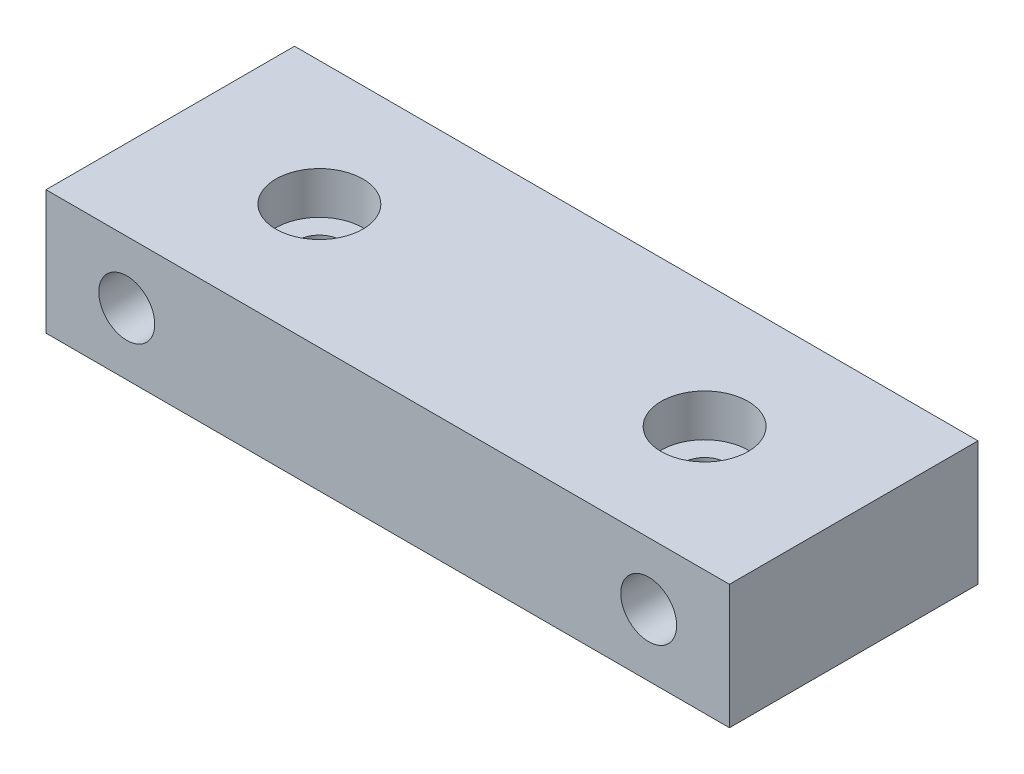
SolidWorks part; units mm, degrees
material "ABS"
ref_plane "Front Plane" through (0, 0, 0) normal (0, 0, 1) x (1, 0, 0)
ref_plane "Top Plane" through (0, 0, 0) normal (0, 1, 0) x (1, 0, 0)
ref_plane "Right Plane" through (0, 0, 0) normal (1, 0, 0) x (0, 0, -1)
sketch "Sketch1" plane through (0, 0, 0) normal (0, 1, 0) x (1, 0, 0)
  line L1 (-27.5, -10) -> (27.5, -10)
  line L2 (-27.5, -10) -> (-27.5, 10)
  line L3 (-27.5, 10) -> (27.5, 10)
  line L4 (27.5, -10) -> (27.5, 10)
  line L5 (-27.5, -10) -> (27.5, 10) construction
  line L6 (-27.5, 10) -> (27.5, -10) construction
  point P0 (0, 0)
  dimension "D1" = 55
  dimension "D2" = 20
extrude "Boss-Extrude1" add sketch "Sketch1" along normal blind 10
sketch "Sketch2" plane through (0, 0, 10) normal (0, 0, 1) x (1, 0, 0)
  line L0 (-27.5, 0) -> (27.5, 0) construction
  line L1 (-27.5, 10) -> (-27.5, 0) construction
  circle A0 centre (-21, 5) radius 2.25
  circle A1 centre (21, 5) radius 2.25
  dimension "D1" = 4.5
  dimension "D4" = 4.5
  dimension "D2" = 5
  dimension "D3" = 6.5
  dimension "D5" = 42
extrude "Cut-Extrude1" cut sketch "Sketch2" against normal through all
sketch "Sketch3" plane through (0, 10, 0) normal (0, 1, 0) x (1, 0, 0)
  line L0 (27.5, -10) -> (27.5, 10) construction
  line L1 (-27.5, 10) -> (-27.5, -10) construction
  circle A0 centre (-15.5, 0) radius 1.75
  circle A1 centre (15.5, 0) radius 1.75
  dimension "D1" = 3.5
  dimension "D2" = 3.5
  dimension "D3" = 12
  dimension "D4" = 12
extrude "Cut-Extrude2" cut sketch "Sketch3" against normal through all
hole_wizard "CBORE for M3 Hex Socket Head Cap Screw1" positions "Sketch4" profile "Sketch5" counterbore size "M3" standard "ISO" end condition through all
sketch "Sketch4" plane through (0, 10, 0) normal (0, 1, 0) x (1, 0, 0)
  point P0 (-15.5, 0)
  point P3 (15.5, 0)
sketch "Sketch5" plane through (-15.5, 10, 0) normal (1, 0, 0) x (0, 0, 1)
  line L0 (0, 0) -> (0, 10)
  line L1 (0, 10) -> (1.7, 10)
  line L3 (1.7, 10) -> (1.7, 3.4)
  line L4 (1.7, 3.4) -> (3.5, 3.4)
  line L5 (3.5, 3.4) -> (3.5, 0)
  line L7 (3.5, 0) -> (0, 0)
  line L11 (0, -6.35) -> (0, 107.95) construction
  dimension "Thru Hole Dia." = 3.4
  dimension "Thru Hole Depth" = 10
  dimension "C'Bore Dia." = 7
  dimension "C'Bore Depth" = 3.4
sketch "Sketch6" plane through (0, 0, -10) normal (0, 0, -1) x (-1, 0, 0)
  line L13 (-16.7276, 5) -> (-18.8638, 8.7)
  line L14 (-18.8638, 8.7) -> (-23.1362, 8.7)
  line L15 (-23.1362, 8.7) -> (-25.2724, 5)
  line L16 (-25.2724, 5) -> (-23.1362, 1.3)
  line L17 (-23.1362, 1.3) -> (-18.8638, 1.3)
  line L18 (-18.8638, 1.3) -> (-16.7276, 5)
  line L19 (16.7276, 5) -> (18.8638, 1.3)
  line L20 (18.8638, 1.3) -> (23.1362, 1.3)
  line L21 (23.1362, 1.3) -> (25.2724, 5)
  line L22 (25.2724, 5) -> (23.1362, 8.7)
  line L23 (23.1362, 8.7) -> (18.8638, 8.7)
  line L24 (18.8638, 8.7) -> (16.7276, 5)
  circle A0 centre (-21, 5) radius 3.7 construction
  circle A1 centre (21, 5) radius 3.7 construction
  dimension "D1" = 7.4
  dimension "D2" = 7.4
extrude "Cut-Extrude3" cut sketch "Sketch6" against normal blind 4
